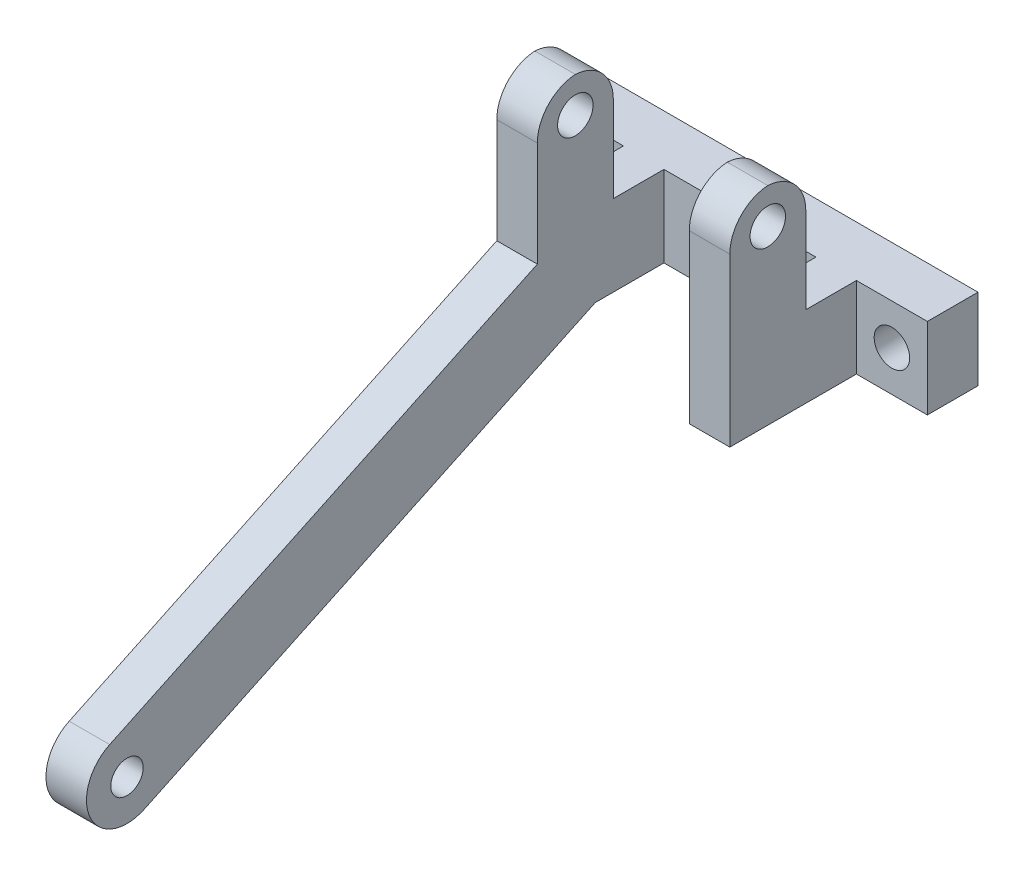
SolidWorks part; units mm, degrees
ref_plane "Front Plane" through (0, 0, 0) normal (0, 0, 1) x (1, 0, 0)
ref_plane "Top Plane" through (0, 0, 0) normal (0, 1, 0) x (1, 0, 0)
ref_plane "Right Plane" through (0, 0, 0) normal (1, 0, 0) x (0, 0, -1)
sketch "Sketch1" plane through (0, 0, 0) normal (0, 0, 1) x (1, 0, 0)
  line L0 (15, 0) -> (-15, 0) construction
  line L1 (-18.5, 4) -> (18.5, 4)
  line L2 (-18.5, 4) -> (-18.5, -4)
  line L3 (-18.5, -4) -> (18.5, -4)
  line L4 (18.5, 4) -> (18.5, -4)
  line L5 (-18.5, 4) -> (18.5, -4) construction
  line L6 (-18.5, -4) -> (18.5, 4) construction
  line L7 (0, -4) -> (0, 4) construction
  circle A0 centre (-15, 0) radius 1.75
  circle A1 centre (15, 0) radius 1.75
  point P0 (0, 0)
  point P12 (0, 0)
  dimension "D3" = 3.5
  dimension "D1" = 37
  dimension "D2" = 8
  dimension "D4" = 15
extrude "Boss-Extrude1" add sketch "Sketch1" along normal blind 5
sketch "Sketch2" plane through (0, 0, 5) normal (0, 0, 1) x (1, 0, 0)
  line L0 (0, 4) -> (0, -4) construction
  line L1 (18.5, 4) -> (-18.5, 4) construction
  line L2 (-18.5, -4) -> (18.5, -4) construction
  line L3 (11.5, -4) -> (7.5, 4) construction
  line L4 (-11.5, 4) -> (-7.5, 4)
  line L5 (-11.5, 4) -> (-11.5, -4)
  line L6 (-11.5, -4) -> (-7.5, -4)
  line L7 (-7.5, 4) -> (-7.5, -4)
  line L8 (-11.5, 4) -> (-7.5, -4) construction
  line L9 (-11.5, -4) -> (-7.5, 4) construction
  line L10 (11.5, 4) -> (7.5, -4) construction
  line L11 (7.5, 4) -> (7.5, -4)
  line L12 (11.5, -4) -> (7.5, -4)
  line L13 (11.5, 4) -> (11.5, -4)
  line L14 (11.5, 4) -> (7.5, 4)
  point P6 (-9.5, 0)
  point P15 (9.5, 0)
  dimension "D1" = 7.5
  dimension "D2" = 4
extrude "Boss-Extrude2" add sketch "Sketch2" along normal blind 12.5
sketch "Sketch4" plane through (0, 4, 0) normal (0, 1, 0) x (1, 0, 0)
  line L0 (-7.5, -17.5) -> (-7.5, -5) construction
  line L1 (-11.5, -17.5) -> (-7.5, -17.5)
  line L2 (-11.5, -17.5) -> (-11.5, -10)
  line L3 (-11.5, -10) -> (-7.5, -10)
  line L4 (-7.5, -17.5) -> (-7.5, -10)
  line L5 (0, 0) -> (0, -5) construction
  line L6 (7.5, -5) -> (-7.5, -5) construction
  line L7 (7.5, -17.5) -> (7.5, -10)
  line L8 (11.5, -10) -> (7.5, -10)
  line L9 (11.5, -17.5) -> (11.5, -10)
  line L10 (11.5, -17.5) -> (7.5, -17.5)
  dimension "D1" = 7.5
extrude "Boss-Extrude3" add sketch "Sketch4" along normal blind 12.5
sketch "Sketch3" plane through (-11.5, 0, 0) normal (-1, 0, 0) x (0, 0, 1)
  line L0 (10, 13) -> (17.5, 13) construction
  line L4 (10, 16.5) -> (10, 4) construction
  line L5 (17.5, 16.5) -> (17.5, -4) construction
  line L6 (13.75, 13) -> (13.75, 16.5) construction
  line L7 (10, 16.5) -> (17.5, 16.5) construction
  circle A0 centre (13.75, 13) radius 1.75
  dimension "D1" = 3.5
  dimension "D2" = 13
extrude "Cut-Extrude1" cut sketch "Sketch3" against normal through all
fillet "Fillet1" radius 4 4 edges at (-9.5, 16.5, 10) (9.5, 16.5, 10) (9.5, 16.5, 17.5) (-9.5, 16.5, 17.5)
sketch "Sketch5" plane through (-7.5, 0, 0) normal (1, 0, 0) x (0, 0, -1)
  line L0 (-10, 12.5) -> (-10, 4) construction
  line L1 (-10, 6.5) -> (-13, 6.5)
  line L2 (-10, 6.5) -> (-10, 1.5)
  line L3 (-10, 1.5) -> (-13, 1.5)
  line L4 (-13, 6.5) -> (-13, 1.5)
  line L5 (-10, 4) -> (-5, 4) construction
  dimension "D1" = 3
  dimension "D2" = 5
  dimension "D3" = 2.5
extrude "Boss-Extrude4" [suppressed] add sketch "Sketch5" along normal up to next
sketch "Sketch6" plane through (-11.5, 0, 0) normal (-1, 0, 0) x (0, 0, 1)
  line L0 (56.2934, -25.0486) -> (11.7824, -4)
  line L1 (17.5, -4) -> (5, -4) construction
  line L2 (11.7824, -4) -> (17.5, 2.1456)
  line L3 (13.75, 13) -> (58.0033, -21.4326) construction
  line L4 (17.5, 2.1456) -> (59.7133, -17.8165)
  line L5 (59.7133, -17.8165) -> (56.2934, -25.0486) construction
  line L6 (13.75, 13) -> (13.75, -4) construction
  line L7 (17.5, 12.5) -> (17.5, -4) construction
  circle A0 centre (58.0033, -21.4326) radius 1.6
  arc A1 (56.2934, -25.0486) -> (59.7133, -17.8165) centre (58.0033, -21.4326) ccw
  dimension "D1" = 3.2
  dimension "D2" = 8
  dimension "D3" = 52.114
  dimension "D4" = 56.071
  dimension "D5" = 1.9676
extrude "Boss-Extrude5" add sketch "Sketch6" against normal up to surface (4 mm away) up to face at (-7.5, 11.25, 13.75)
equation "\"X-ROD-SPACING\"=45"
equation "\"Y-ROD-SPACING\"=75"
equation "\"Z-ROD-SPACING\"=17.5"
equation "\"Y-BED-OFFSET\"=2"
equation "\"Y-BED-ROD-INSET\"=3.5"
equation "\"Y-BED-SCREW-SPACING\"=209"
equation "\"Y-BED-SCREW-CUTOUT-SLOT-HEIGHT\"=2"
equation "\"T-SLOT-NUT-FILLET-RADIUS\"=0.25"
equation "\"T-SLOT-SCREW-SHAFT-RADIUS\"=1.75"
equation "\"T-SLOT-SCREW-SHAFT-CUTOUT-LENGTH\"=10.5"
equation "\"T-SLOT-NUT-DEPTH\"=4.2"
equation "\"T-SLOT-NUT-WIDTH\"=3"
equation "\"T-SLOT-NUT-END-DISTANCE\"=8"
equation "\"ACRYLIC-THICKNESS\"=10"
equation "\"ACRYLIC-THICKNESS2\"=4.5"
equation "\"ACRYLIC-TAB-CUTOUT-SIZE\"=\"ACRYLIC-THICKNESS\"+\"ACRYLIC-TAB-TOLERANCE\"*2"
equation "\"ACRYLIC-TAB-TOLERANCE\"=.1"
equation "\"ACRYLIC-TAB-WIDTH\"=\"ACRYLIC-THICKNESS\""
equation "\"ACRYLIC-M3-HOLE\"=3.1"
equation "\"SMOOTHROD-CAP-SCREW-DISTANCE\"=20"
equation "\"FRAME-WIDTH-INNER\"=370"
equation "\"NEMA17-HOLE-SPACING\"=31"
equation "\"NEMA17-CENTRAL-CUTOUT\"=22.5"
equation "\"Z-BRACKET-REACH\"=55"
equation "\"Z-ROD-INSET\"=16"
equation "\"TOP-BRACKET-SPACING\"=40"
equation "\"SMOOTHROD-X-LENGTH\"=350"
equation "\"SMOOTHROD-Y-LENGTH\"=350"
equation "\"SMOOTHROD-Z-LENGTH\"=350"
equation "\"SMOOTHROD-TIGHTENING-HEADROOM\"=.25"
equation "\"LEADSCREW-Z-LENGTH\"=300"
equation "\"SCREW-LENGTH-FRAME\"=\"ACRYLIC-THICKNESS\" + 10"
equation "\"SCREW-LENGTH-MOTOR\"=\"ACRYLIC-THICKNESS\" + 5"
equation "\"SCREW-LENGTH-EXTRUDER\"=28"
equation "\"SCREW-HEAD-RADIUS\"=6"
equation "\"PRINTED-X-SMOOTHROD-DIAMETER\"=8.2"
equation "\"PRINTED-X-SMOOTHROD-CUTOUT\"=10"
equation "\"PRINTED-X-BASE-HEIGHT\"=10"
equation "\"PRINTED-LM8UU-CUTOUT-SIZE\"=15.25"
equation "\"PRINTED-LM8UU-CUTOUT-LENGTH\"=24.5"
equation "\"PRINTED-X-IDLER-HEIGHT\"=16"
equation "\"PSU-MOUNTING-WIDTH\"=95"
equation "\"PSU-MOUNTING-HEIGHT\"=177"
equation "\"Y-BELT-TO-ROD-DISTANCE\"=20"
equation "\"SPOOL-HOLDER-ROD-SPACING\"=150"
equation "\"ACRYLIC-X-CARRIAGE-WIDTH\"=55"
equation "\"ACRYLIC-X-CARRIAGE-HEIGHT\"=75"
equation "\"ACRYLIC-X-CARRIAGE-LM8UU-CUTOUT-WIDTH\"=24.25"
equation "\"ACRYLIC-X-CARRIAGE-LM8UU-CUTOUT-HEIGHT\"=11.5"
equation "\"ACRYLIC-X-CARRIAGE-SCREW-SPACING-X\"=15"
equation "\"ACRYLIC-X-CARRIAGE-SCREW-SPACING-Y\"=33"
equation "\"ACRYLIC-X-CARRIAGE-CENTER-TAB-SPACING\"=14"
equation "\"ACRYLIC-X-CARRIAGE-EXTRUDER-OFFSET\"=26"
equation "\"ACRYLIC-X-CARRIAGE-EXTRUDER-ANGLE\"=90"
equation "\"ACRYLIC-X-CARRIAGE-EXTRUDER-SHELF-DEPTH\"=\"ACRYLIC-X-CARRIAGE-EXTRUDER-OFFSET\" + 28"
equation "\"ACRYLIC-X-CARRIAGE-EXTRUDER-BRACE-SPACING\"=23"
equation "\"ACRYLIC-X-CARRIAGE-EXTRUDER-BRACE-TAB-OFFSET\"=20"
equation "\"ACRYLIC-X-CARRIAGE-EXTRUDER-BRACE-HEIGHT\"=35"
equation "\"ACRYLIC-X-CARRIAGE-EXTRUDER-BRACE-SCREW-SPACING\"=22"
equation "\"ACRYLIC-X-CARRIAGE-DUAL-WIDTH-MULTIPLIER\"=1.65"
equation "\"ACRYLIC-X-CARRIAGE-DUAL-HOTEND-SPACING\"=42"
equation "\"ACRYLIC-X-CARRIAGE-DUAL-WIDTH\"=103"
equation "\"ACRYLIC-X-CARRIAGE-DUAL-HOTEND-SEPARATION\"=35"
equation "\"ACRYLIC-X-CARRIAGE-DUAL-MOUNT-PLATE-DEPTH\"=76"
equation "\"ACRYLIC-X-CARRIAGE-DUAL-MOUNT-BRACE-WIDTH\"=45"
equation "\"ACRYLIC-X-CARRIAGE-DUAL-MOUNT-SCREW-WIDTH\"=40"
equation "\"D3@Sketch1\"=3.5"
equation "\"PRINTED-M3-HOLE\"=3.5"
equation "\"BLOWER-FAN-WIDTH\"=15"
equation "\"D1@Sketch2\"=\"BLOWER-FAN-WIDTH\"/2"
